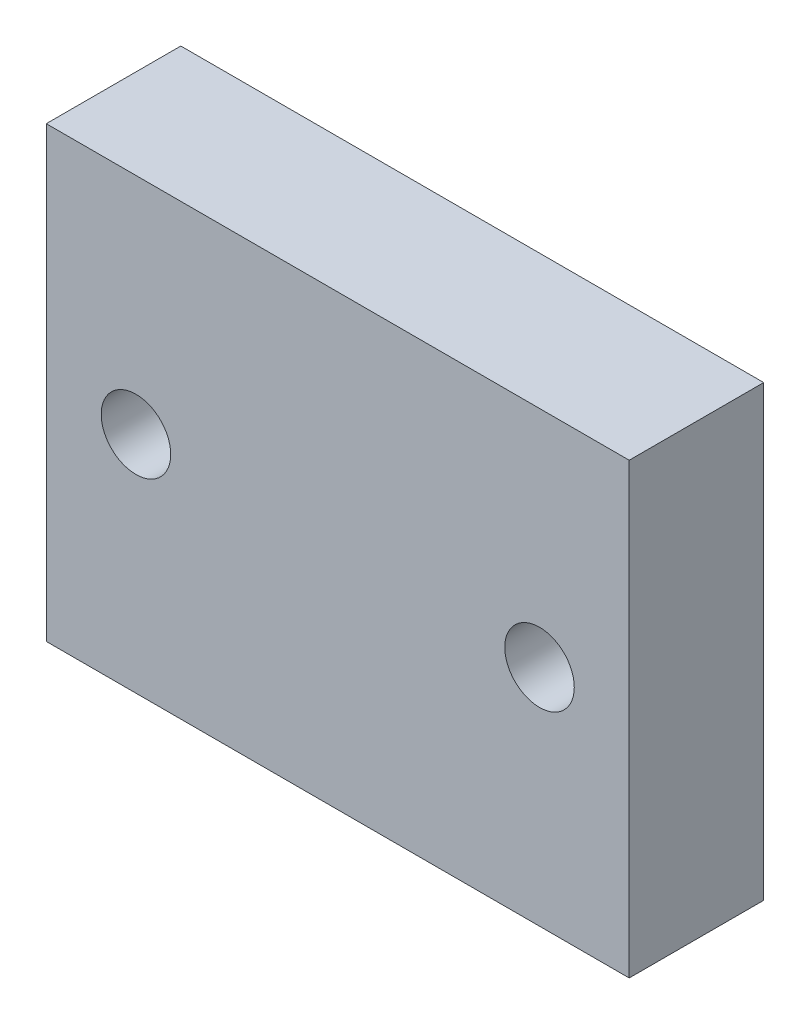
SolidWorks part; units mm, degrees
ref_plane "Front" through (0, 0, 0) normal (0, 0, 1) x (1, 0, 0)
ref_plane "Top" through (0, 0, 0) normal (0, 1, 0) x (1, 0, 0)
ref_plane "Right" through (0, 0, 0) normal (1, 0, 0) x (0, 0, -1)
sketch "Sketch1" plane through (0, 0, 0) normal (0, 0, 1) x (1, 0, 0)
  line L1 (13, -10) -> (-13, -10)
  line L2 (13, -10) -> (13, 10)
  line L3 (13, 10) -> (-13, 10)
  line L4 (-13, -10) -> (-13, 10)
  line L5 (13, -10) -> (-13, 10) construction
  line L6 (13, 10) -> (-13, -10) construction
  circle A2 centre (9, 0) radius 1.55
  circle A3 centre (-9, 0) radius 1.55
  point P0 (0, 0)
  dimension "D3" = 3.1
  dimension "D4" = 3.1
  dimension "D5" = 9
  dimension "D6" = 9
  dimension "D1" = 20
  dimension "D2" = 26
extrude "Boss-Extrude1" add sketch "Sketch1" along normal blind 6
sketch "Sketch4" plane through (0, 0, 0) normal (0, 0, -1) x (-1, 0, 0)
  line L1 (-5, 4) -> (5, 4)
  line L2 (-5, 4) -> (-5, 2)
  line L3 (-5, 2) -> (5, 2)
  line L4 (5, 4) -> (5, 2)
  line L5 (-5, 4) -> (5, 2) construction
  line L6 (-5, 2) -> (5, 4) construction
  line L8 (-13, 10) -> (13, 10) construction
  point P4 (0, 3)
  dimension "D1" = 2
  dimension "D2" = 6
  dimension "D3" = 10
extrude "Cut-Extrude3" cut sketch "Sketch4" against normal blind 1
chamfer "Chamfer1" distance 1 angle 45 1 edges at (0, 4, 0)
